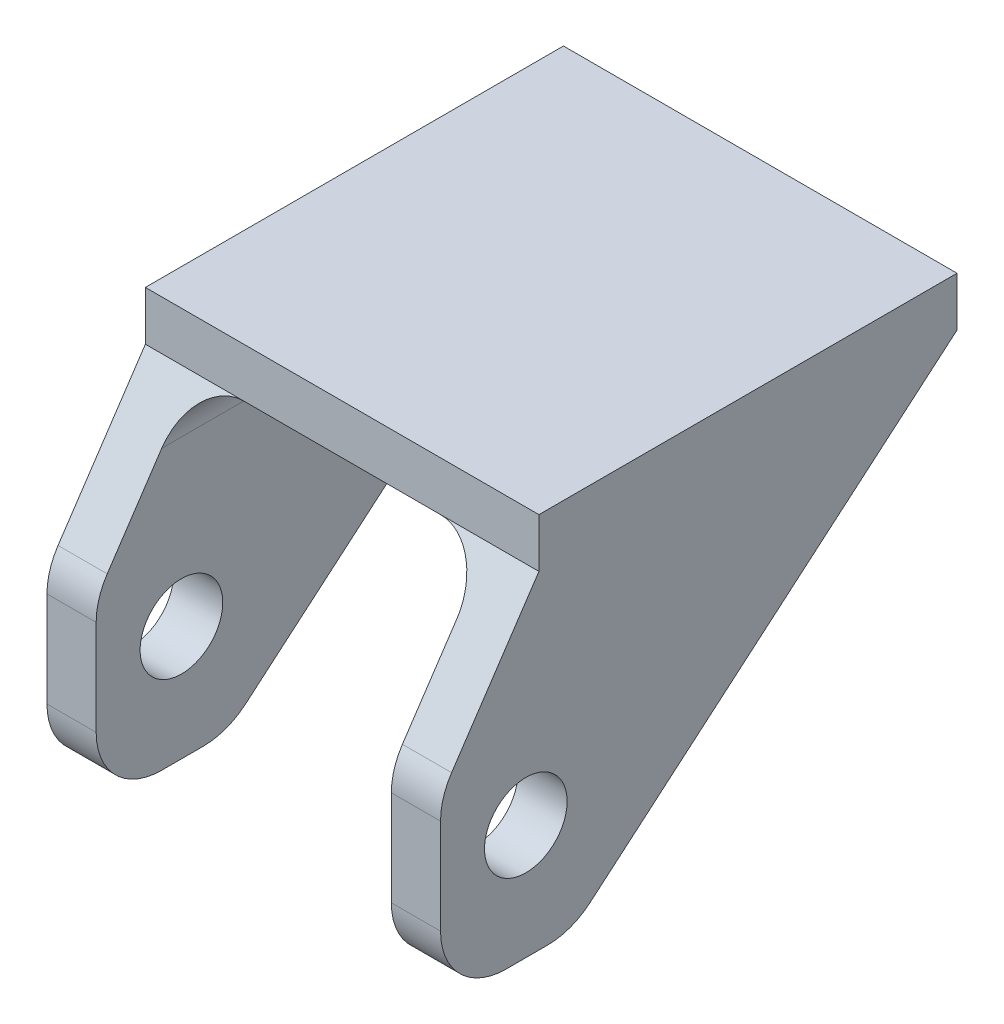
SolidWorks part; units mm, degrees
note: The reader was unsure of these and kept them because the rebuilt part matched: shared geometry of "Sketch1<3>".
material "6061-T6 (SS)"
ref_plane "Front Plane" through (0, 0, 0) normal (0, 0, 1) x (1, 0, 0)
ref_plane "Top Plane" through (0, 0, 0) normal (0, 1, 0) x (1, 0, 0)
ref_plane "Right Plane" through (0, 0, 0) normal (1, 0, 0) x (0, 0, -1)
sketch "Sketch1" plane through (0, 0, 0) normal (0, 1, 0) x (1, 0, 0)
  line L1 (-14.2875, -25) -> (14.2875, -25)
  line L2 (-14.2875, -25) -> (-14.2875, 25)
  line L3 (-14.2875, 25) -> (14.2875, 25)
  line L4 (14.2875, -25) -> (14.2875, 25)
  line L5 (-14.2875, -25) -> (14.2875, 25) construction
  line L6 (-14.2875, 25) -> (14.2875, -25) construction
  line L7 (14.2875, 25) -> (19.05, 25)
  line L8 (14.2875, 25) -> (14.2875, -25)
  line L9 (14.2875, -25) -> (19.05, -25)
  line L10 (19.05, 25) -> (19.05, -25)
  line L11 (-14.2875, 25) -> (-19.05, 25)
  line L12 (-14.2875, 25) -> (-14.2875, -25)
  line L13 (-14.2875, -25) -> (-19.05, -25)
  line L14 (-19.05, 25) -> (-19.05, -25)
  point P0 (0, 0)
  dimension "D1" = 38.1
  dimension "D2" = 50
  dimension "D3" = 4.7625
  dimension "D4" = 4.7625
extrude "Boss-Extrude1" add sketch "Sketch1" along normal blind 4.7625 contours L11 L14 L13 L2 | L1 L4 L3 L2 | L10 L7 L4 L9
extrude "Boss-Extrude2" add sketch "Sketch1<3>" against normal blind 31.75 contours L11 L14 L13 L2 | L10 L7 L4 L9
sketch "Sketch1<3>" plane through (0, 0, 0) normal (0, 1, 0) x (1, 0, 0) same geometry as "Sketch1"
sketch "Sketch3" plane through (19.05, 0, 0) normal (1, 0, 0) x (0, 0, -1)
  line L0 (25, 0) -> (-12.3, -31.75)
  line L1 (25, 0) -> (-25, 0) construction
  line L2 (-12.3, -31.75) -> (-25, -31.75)
  line L3 (-25, -14.2476) -> (-15.475, 0)
  line L4 (-25, 4.7625) -> (-25, -31.75)
  line L5 (-25, -31.75) -> (25, -31.75)
  line L6 (25, -31.75) -> (25, 4.7625)
  line L7 (25, 4.7625) -> (-25, 4.7625)
  line L8 (-25, 4.7625) -> (-25, -31.75)
  line L9 (-25, -31.75) -> (25, -31.75)
  line L10 (25, -31.75) -> (25, 4.7625)
  line L11 (25, 4.7625) -> (-25, 4.7625)
  line L12 (-25, 0) -> (-25, -31.75)
  line L13 (-15.475, 0) -> (-15.475, 4.7625)
  line L14 (-25, 4.7625) -> (-25, -31.75) construction
  circle A0 centre (-16.745, -20.6375) radius 4
  line M10 (-25, 4.7625) -> (-25, -31.75)
  line M11 (-25, -31.75) -> (25, -31.75)
  line M12 (25, -31.75) -> (25, 4.7625)
  dimension "D4" = 8
  dimension "D2" = 10.414
  dimension "D3" = 12.7
  dimension "D5" = 25.4
  dimension "D6" = 9.525
  dimension "D7" = 1.27
  dimension "D1" = 0
extrude "Cut-Extrude1" cut sketch "Sketch3" against normal through all contours L0 M12 M11 | L3 L13 L11 L8 M10 | A0
fillet "Fillet1" radius 6.35 6 edges at (-16.6688, -31.75, 25) (16.6688, -31.75, 25) (16.6688, -31.75, 12.3) (-16.6688, -31.75, 12.3) (16.6688, -14.2476, 25) (-16.6688, -14.2476, 25)
fillet "Fillet2" radius 4.7625 2 edges at (14.2875, 0, -4.7625) (-14.2875, 0, -4.7625)
